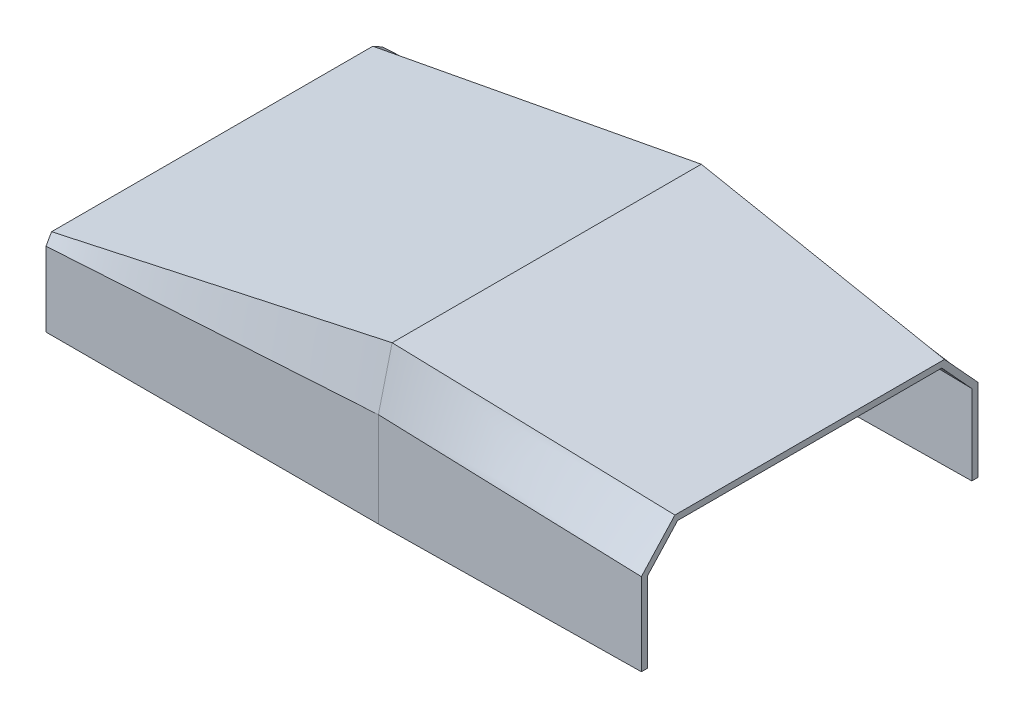
SolidWorks part; units mm, degrees
ref_plane "Front Plane" through (0, 0, 0) normal (0, 0, 1) x (1, 0, 0)
ref_plane "Top Plane" through (0, 0, 0) normal (0, 1, 0) x (1, 0, 0)
ref_plane "Right Plane" through (0, 0, 0) normal (1, 0, 0) x (0, 0, -1)
sketch "Sketch1" plane through (0, 0, 100.1804) normal (0, 0, 1) x (1, 0, 0)
  line L0 (75.2497, 152.1811) -> (225.2497, 136.4155) construction
  line L1 (225.2497, 72.5559) -> (225.2497, 136.4155) construction
  line L2 (-114.3316, 95.9059) -> (-114.3316, 114.5559) construction
  line L3 (-114.3316, 97.4059) -> (-114.3316, 94.4059) construction
  line L4 (-114.3316, 114.5559) -> (75.2497, 152.1811) construction
  line L5 (-114.3316, 114.5559) -> (57.7696, 114.5559) construction
  dimension "D1" = 42
  dimension "D3" = 65
  dimension "D2" = 6
  dimension "D4" = 150
ref_plane "Plane3" through (-114.3315, 0, -0.0001) normal (-1, 0, 0) x (0, 0, 1)
ref_plane "Plane4" through (75.2497, 0, 0) normal (-1, 0, 0) x (0, 0, 1)
sketch "Sketch4" plane through (75.2497, 0, 0) normal (-1, 0, 0) x (0, 0, 1)
  line L0 (192.6804, 70.0559) -> (7.6804, 70.0559) construction
  line L1 (7.6804, 70.0559) -> (7.6804, 120.5559)
  line L2 (192.6804, 70.0559) -> (192.6804, 120.5559)
  line L3 (113.1004, 70.0559) -> (117.1004, 70.0559) construction
  line L4 (7.6804, 81.5559) -> (7.6804, 72.5559) construction
  line L5 (192.6804, 81.5559) -> (192.6804, 72.5559) construction
  line L6 (-23.4411, 120.5559) -> (246.3709, 120.5559) construction
  line L7 (184.8572, 152.1811) -> (15.5035, 152.1811)
  line L8 (7.6804, 70.0559) -> (4.1804, 70.0559)
  line L9 (4.1804, 70.0559) -> (4.1804, 124.0559)
  line L10 (192.6804, 70.0559) -> (196.1804, 70.0559)
  line L11 (196.1804, 70.0559) -> (196.1804, 124.0559)
  line L12 (-33.1636, 124.0559) -> (257.1203, 124.0559) construction
  line L14 (15.5035, 152.1811) -> (7.6804, 120.5559)
  line L15 (184.8572, 152.1811) -> (192.6804, 120.5559)
  line L16 (196.1804, 124.0559) -> (188.3572, 155.6811)
  line L17 (188.3572, 155.6811) -> (12.0035, 155.6811)
  line L18 (12.0035, 155.6811) -> (4.1804, 124.0559)
  point P13 (100.1804, 152.1811)
  point P25 (100.1804, 151.3325)
  dimension "D1" = 3.5
  dimension "D3" = 3.5
  dimension "D7" = 54
  dimension "D2" = 3.5
  dimension "D4" = 269.812
  dimension "D5" = 3.5
ref_plane "Plane5" through (225.2497, 0, 0) normal (-1, 0, 0) x (0, 0, 1)
sketch "Sketch5" plane through (225.2497, 0, 0) normal (-1, 0, 0) x (0, 0, 1)
  line L0 (7.6804, 72.0559) -> (7.6804, 117.683)
  line L1 (7.6804, 117.683) -> (24.8444, 136.4155)
  line L2 (24.8444, 136.4155) -> (175.5163, 136.4155)
  line L3 (175.5163, 136.4155) -> (192.6804, 117.683)
  line L4 (192.6804, 117.683) -> (192.6804, 72.0559)
  line L5 (192.6804, 72.0559) -> (196.1804, 72.0559)
  line L6 (196.1804, 72.0559) -> (196.1804, 119.044)
  line L7 (196.1804, 119.044) -> (177.0564, 139.9155)
  line L8 (177.0564, 139.9155) -> (23.3043, 139.9155)
  line L9 (23.3043, 139.9155) -> (4.1804, 119.044)
  line L10 (4.1804, 119.044) -> (4.1804, 72.0559)
  line L11 (4.1804, 72.0559) -> (7.6804, 72.0559)
  line L13 (7.6804, 81.5559) -> (7.6804, 72.5559) construction
  line L14 (192.6804, 81.5559) -> (192.6804, 72.5559) construction
  line L16 (132.6804, 72.0559) -> (189.1804, 72.0559) construction
  point P20 (100.1804, 139.9155)
  point P23 (13.7423, 129.4797)
  dimension "D1" = 3.5
  dimension "D2" = 3.5
  dimension "D3" = 3.5
  dimension "D5" = 3.5
  dimension "D6" = 3.5
sketch "Sketch6" plane through (0, 0, 0) normal (0, 0, 1) x (1, 0, 0)
  circle A0 centre (188.2497, 50.5559) radius 35
  dimension "D1" = 70
sketch "Sketch7" plane through (0, 0, 0) normal (0, 0, 1) x (1, 0, 0)
  line L1 (-122.8751, 60.1739) -> (235.9499, 60.1739)
  line L6 (-122.8751, 60.1739) -> (-122.8751, 158.8012)
  line L7 (-122.8751, 158.8012) -> (235.9499, 158.8012)
  line L8 (235.9499, 60.1739) -> (235.9499, 158.8012)
sketch "Sketch8" plane through (-114.3315, 0, -0.0001) normal (-1, 0, 0) x (0, 0, 1)
  line L0 (4.1803, 70.0559) -> (7.6803, 70.0559)
  line L1 (7.6803, 70.0559) -> (7.6803, 112.8434)
  line L2 (7.6803, 70.0559) -> (7.6803, 120.5559) construction
  line L3 (7.6803, 112.8434) -> (10.6961, 114.5559)
  line L4 (10.6961, 114.5559) -> (187.8278, 114.5559)
  line L5 (187.8278, 114.5559) -> (192.6803, 106.0105)
  line L6 (192.6803, 70.0559) -> (192.6803, 120.5559) construction
  line L7 (192.6803, 106.0105) -> (192.6803, 70.0559)
  line L8 (192.6803, 70.0559) -> (196.1803, 70.0559)
  line L9 (196.1803, 70.0559) -> (196.1803, 112.4646)
  line L10 (196.1803, 70.0559) -> (196.1803, 124.0559) construction
  line L11 (196.1803, 112.4646) -> (193.0053, 118.0559)
  line L12 (193.0053, 118.0559) -> (9.7716, 118.0559)
  line L13 (9.7716, 118.0559) -> (4.1803, 114.8809)
  line L14 (4.1803, 70.0559) -> (4.1803, 124.0559) construction
  line L15 (4.1803, 114.8809) -> (4.1803, 70.0559)
  dimension "D1" = 3.5
  dimension "D2" = 3.5
  dimension "D3" = 119.59
loft "Loft2" add profiles "Sketch8", "Sketch4" connector at (-114.3315, 118.0559, 9.7716) connector at (75.2497, 155.6811, 12.0035)
loft "Loft3" add profiles "Sketch4<4>", "Sketch5" start constraint default connector at (75.2497, 70.0559, 196.1804) connector at (225.2497, 72.0559, 196.1804)
sketch "Sketch4<4>" plane through (75.2497, 0, 0) normal (-1, 0, 0) x (0, 0, 1) same geometry as "Sketch4"
